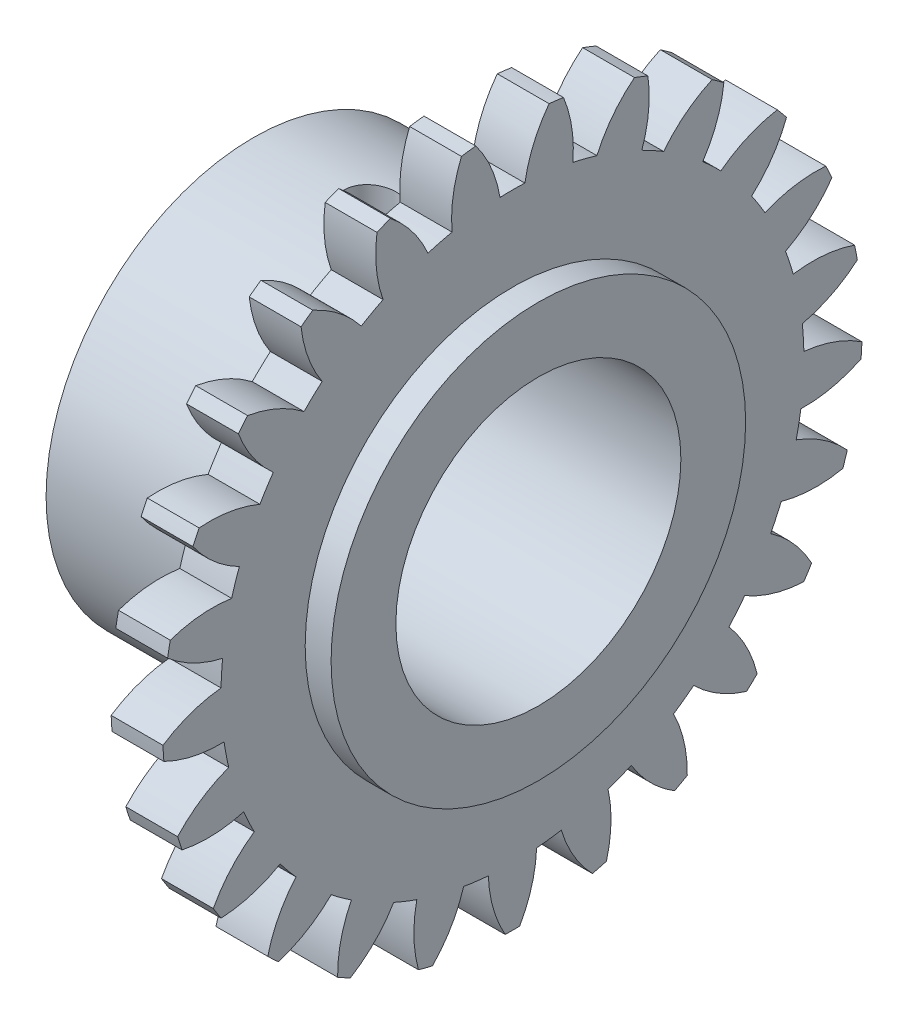
SolidWorks part; units mm, degrees
material "Alliage de zinc AC41A, brut"
ref_plane "Plane1" through (0, 0, 0) normal (0, 0, 1) x (1, 0, 0)
ref_plane "Plane2" through (0, 0, 0) normal (0, 1, 0) x (1, 0, 0)
ref_plane "Plane3" through (0, 0, 0) normal (1, 0, 0) x (0, 0, -1)
sketch "HoldingSke" plane through (0, 0, 0) normal (0, 1, 0) x (1, 0, 0)
  line L0 (0, 0) -> (0.9063, -0.4226)
  line L1 (-15, 0) -> (100, 0) construction
  line L2 (0, 0) -> (-2.1039, 2.3779)
  line L3 (0, 0) -> (-11.863, 4.5341)
  line L4 (0, 0) -> (7.8269, 3.6497)
  line L5 (0, 0) -> (-46.8476, -17.4728)
  line L6 (0, 0) -> (-1.6579, -1.1186)
  line L7 (-2.1039, 2.3779) -> (8.6586, 51.2059)
  line L8 (-76.2, 54.61) -> (-75.9, 54.61)
  line L9 (-71.009, 38.7566) -> (-53.1078, 45.2721)
  line L10 (-76.2, 71.12) -> (104.1128, 71.12)
  line L11 (0, 0) -> (-2, 0)
  line L12 (-76.2, 101.6) -> (-76.162, 101.6)
  line L13 (24.9733, 27.94) -> (52.9518, 28.4284)
  line L14 (24.9733, 27.94) -> (24.9743, 27.94)
  line L15 (24.9733, 27.94) -> (100.4006, 29.5858)
  line L16 (-63.627, -1) -> (-12.827, -1)
  circle A0 centre (0, 0) radius 1
  circle A1 centre (0, 0) radius 11.249
  circle A2 centre (0, 0) radius 37.5
  circle A3 centre (0, 0) radius 5.5
  dimension "Num_teeth" = 25
  dimension "Pitch_radius" = 180.3128
  dimension "Width" = 2
  dimension "Thickness" = 2
sketch "BasProSke" plane through (0, 0, 0) normal (0, 1, 0) x (1, 0, 0)
  line L0 (-10, 0) -> (60, 0) construction
  line L1 (0, 0) -> (0, 13.5)
  line L2 (0, 0) -> (2, 0)
  line L3 (2, 0) -> (2, 13.5)
  line L4 (2, 13.5) -> (0, 13.5)
  dimension "Thickness" = 2
  dimension "Diameter" = 27
revolve "Base-Revolve" add sketch "BasProSke" angle 360 about L0
sketch "TooCutSke" plane through (0, 0, 0) normal (1, 0, 0) x (0, 0, -1)
  line L1 (0, 0) -> (0, 107) construction
  line L2 (0, 0) -> (-0.8514, 12.471) construction
  line L3 (0, 0) -> (-3.1282, 24.7619) construction
  line L4 (-0.8514, 12.471) -> (-1.5641, 12.3809) construction
  arc A0 (0.4801, 11.2388) -> (-0.4801, 11.2388) centre (0, 0) ccw
  arc A1 (1.4322, 13.4494) -> (-1.4322, 13.4494) centre (0, 0) ccw
  circle A2 centre (0, 0) radius 12.5 construction
  circle A3 centre (0, 0) radius 11.7462 construction
  arc A4 (-0.4801, 11.2388) -> (-1.4322, 13.4494) centre (-5.4133, 10.4244) ccw
  arc A5 (1.4322, 13.4494) -> (0.4801, 11.2388) centre (5.4133, 10.4244) ccw
extrude "ToothCut" cut sketch "TooCutSke" along normal through all
fillet "Breaks" [suppressed] radius 0.02 tangent propagation no
fillet "RootFillets" [suppressed] radius 0.251
pattern_circular "TeethCuts" count 25 every 14.4 about axis through (-10, 0, 0) along (1, 0, 0) of "ToothCut", "RootFillets", "Breaks"
sketch "HubNeaOneSke" plane through (0, 0, 0) normal (-1, 0, 0) x (0, 0, 1)
  circle A0 centre (0, 0) radius 11.249
  dimension "Diameter" = 22.498
extrude "HubNearOne" [suppressed] add sketch "HubNeaOneSke" along normal blind 48.0001
sketch "HubNeaBotSke" plane through (0, 0, 0) normal (-1, 0, 0) x (0, 0, 1)
  circle A0 centre (0, 0) radius 11.249
  dimension "Diameter" = 22.498
extrude "HubNearBoth" [suppressed] add sketch "HubNeaBotSke" along normal blind 24
ref_plane "FarPln" through (2, 0, 0) normal (1, 0, 0) x (0, 0, -1)
sketch "HubFarSke" plane through (2, 0, 0) normal (1, 0, 0) x (0, 0, -1)
  circle A0 centre (0, 0) radius 11.249
  dimension "Diameter" = 22.498
extrude "HubFar" [suppressed] add sketch "HubFarSke" along normal blind 24
sketch "BorSke" plane through (0, 0, 0) normal (1, 0, 0) x (0, 0, -1)
  circle A0 centre (0, 0) radius 5.5
  dimension "Diameter" = 11
extrude "Bore" cut sketch "BorSke" along normal mid plane 100.0001
sketch "KeySke" plane through (0, 0, 0) normal (1, 0, 0) x (0, 0, -1)
  line L0 (-0.4, 0) -> (-0.4, 5.8)
  line L1 (-0.4, 5.8) -> (0.4, 5.8)
  line L2 (0.4, 5.8) -> (0.4, 0)
  line L3 (0, 0) -> (0, 34) construction
  line L4 (-0.4, 0) -> (0.4, 0)
  dimension "Width" = 0.8
extrude "Keyway" [suppressed] cut sketch "KeySke" along normal mid plane 100.0001
pattern_circular "Keyway2" [suppressed] count 2 every 90 about axis through (-10, 0, 0) along (1, 0, 0)
sketch "Esquisse1" plane through (2, 0, 0) normal (1, 0, 0) x (0, 0, -1)
  circle A0 centre (0, 0) radius 5.5
  circle A1 centre (0, 0) radius 8
  dimension "D1" = 11
  dimension "D2" = 16
extrude "Boss.-Extru.1" add sketch "Esquisse1" along normal blind 1
sketch "Esquisse2" plane through (0, 0, 0) normal (-1, 0, 0) x (0, 0, 1)
  circle A0 centre (0, 0) radius 8
  circle A1 centre (0, 0) radius 5.5
  dimension "D1" = 16
  dimension "D2" = 11
extrude "Boss.-Extru.2" add sketch "Esquisse2" along normal blind 8
sketch "Esquisse7" plane through (0, 0, 0) normal (0, 1, 0) x (1, 0, 0)
  line L0 (0, 8) -> (0, -8) construction
  point P0 (-3.5, 0)
  dimension "D1" = 3.5
hole_wizard "Diamètre du perçage Ø2.0 (2)1" positions "Esquisse7" profile "Esquisse4" hole size "Ø2.0" standard "ISO" end condition through all
sketch "Esquisse4" plane through (-3.5, 0, 0) normal (1, 0, 0) x (0, 0, -1)
  line L0 (0, 0) -> (0, 13.4257)
  line L1 (0, 13.4257) -> (1, 13.4257)
  line L2 (1, 13.4257) -> (1, 0)
  line L5 (1, 0) -> (0, 0)
  line L11 (0, -6.35) -> (0, 107.95) construction
  dimension "Diamètre du perçage jusqu'au prochain" = 2
  dimension "Profondeur du perçage jusqu'au prochain" = 13.4257
cosmetic thread "Représentation de filetage1" parameters "D2"=3
equation "' \"Module@HoldingSke\" = 6.35"
equation "' \"Num_teeth@HoldingSke\" = 12"
equation "' \"Ap@HoldingSke\" =  20"
equation "' \"Ap@HoldingSke\" = 20"
equation "' \"Width@HoldingSke\" = 0.5 * 25.4"
equation "' \"Hub_dia@HoldingSke\"= 1 * 25.4"
equation "' \"Hub_dia@HoldingSke\" = 1 * 25.4"
equation "' \"Overall_len@HoldingSke\" = 1.0 * 25.4"
equation "' \"Bore@HoldingSke\" = 0.75 * 25.4"
equation "' \"T_dim@HoldingSke\" = 0.1 * 25.4"
equation "' \"Width@KeySke\" = 0.25 * 25.4"
equation "' \"Show_teeth@HoldingSke\" = 13"
equation "' \"Backlash@HoldingSke\" = 0.009 * 25.4"
equation "' \"Addendum_fac@HoldingSke\" = 1.0"
equation "' \"Dedendum_fac@HoldingSke\" = 1.25"
equation "' \"Dedendum_add@HoldingSke\" = 0.00005 * 25.4"
equation "' \"Clearance_fac@HoldingSke\" = 0.25"
equation "\"Pitch@HoldingSke\" = 1 / \"Module@HoldingSke\""
equation "\"Overcut_dia@TooCutSke\" = (\"Num_teeth@HoldingSke\" + 2 * \"Addendum_fac@HoldingSke\") / \"Pitch@HoldingSke\" + 0.002 * 25.4"
equation "\"Pitch_dia@TooCutSke\" = \"Num_teeth@HoldingSke\" / \"Pitch@HoldingSke\""
equation "\"Base_dia@TooCutSke\" = \"Num_teeth@HoldingSke\" / \"Pitch@HoldingSke\" * cos((\"Ap@HoldingSke\"  * 3.14159265 / 180))"
equation "\"Root_dia@TooCutSke\" = (\"Num_teeth@HoldingSke\" + 2) / \"Pitch@HoldingSke\" - 2 * (\"Addendum_fac@HoldingSke\" + \"Dedendum_fac@HoldingSke\") / \"Pitch@HoldingSke\" - \"Dedendum_add@HoldingSke\" * 2"
equation "\"Half_ang@TooCutSke\" = 180 / \"Num_teeth@HoldingSke\""
equation "\"Half_CT@TooCutSke\" = \"Num_teeth@HoldingSke\" / \"Pitch@HoldingSke\" * sin((3.14159265 / 2 / \"Num_teeth@HoldingSke\")) / 2 - 7 * \"Backlash@HoldingSke\" / 4"
equation "\"Flank_rad@TooCutSke\" = \"Num_teeth@HoldingSke\" / \"Pitch@HoldingSke\" / 5"
equation "\"Radius@RootFillets\" = \"Clearance_fac@HoldingSke\" / \"Pitch@HoldingSke\" + \"Dedendum_add@HoldingSke\""
equation "\"Break_rad@Breaks\" = 0.02 / \"Pitch@HoldingSke\""
equation "\"Thickness@HoldingSke\" = \"Width@HoldingSke\""
equation "\"OAL@HoldingSke\" = \"Thickness@HoldingSke\""
equation "\"MHD@HoldingSke\" = (\"Num_teeth@HoldingSke\" + 2) / \"Pitch@HoldingSke\" - 2 * (\"Addendum_fac@HoldingSke\" + \"Dedendum_fac@HoldingSke\")  / \"Pitch@HoldingSke\" - \"Dedendum_add@HoldingSke\" * 2"
equation "\"MHD@HoldingSke\" = ((sgn( \"MHD@HoldingSke\" - \"Hub_dia@HoldingSke\" )-1)*( \"MHD@HoldingSke\" - \"Hub_dia@HoldingSke\" ))/-2+ \"Hub_dia@HoldingSke\""
equation "\"OAL@HoldingSke\" = ((sgn( \"OAL@HoldingSke\" - \"Overall_len@HoldingSke\" )+1)*( \"OAL@HoldingSke\" - \"Overall_len@HoldingSke\" ))/2 + \"Overall_len@HoldingSke\" + 0.000002 * 25.4"
equation "\"Num_teeth@TeethCuts\" = int( \"Show_teeth@HoldingSke\" ) + 1"
equation "\"Num_teeth@TeethCuts\" = ((sgn( \"Num_teeth@TeethCuts\" - \"Num_teeth@HoldingSke\" )-1)*( \"Num_teeth@TeethCuts\" - \"Num_teeth@HoldingSke\" ))/-2+ \"Num_teeth@HoldingSke\""
equation "\"Num_teeth@TeethCuts\" = ((sgn( \"Num_teeth@TeethCuts\" - 2.0)+1)*( \"Num_teeth@TeethCuts\" - 2.0))/2 +2.0"
equation "\"Angle@TeethCuts\" = 360.0 / \"Num_teeth@HoldingSke\""
equation "\"Diameter@BasProSke\" = (\"Num_teeth@HoldingSke\" + 2 * \"Addendum_fac@HoldingSke\") / \"Pitch@HoldingSke\""
equation "\"Thickness@BasProSke\"  = \"Thickness@HoldingSke\""
equation "' \"Fillet_rad@BasProSke\" =  \"Thickness@HoldingSke\" * 0.05"
equation "' \"Fillet_rad@BasProSke\" = \"Thickness@HoldingSke\" * 0.05"
equation "\"MHD@HoldingSke\" = ((sgn( \"MHD@HoldingSke\" - \"Root_dia@TooCutSke\" )-1)*( \"MHD@HoldingSke\" - \"Root_dia@TooCutSke\" ))/-2+ \"Root_dia@TooCutSke\""
equation "\"Diameter@HubNeaOneSke\" = \"MHD@HoldingSke\""
equation "\"Length@HubNearOne\" = \"OAL@HoldingSke\" - \"Thickness@BasProSke\""
equation "\"Diameter@HubNeaBotSke\" = \"MHD@HoldingSke\""
equation "\"Length@HubNearBoth\" = ( \"OAL@HoldingSke\" - \"Thickness@BasProSke\" ) / 2.0"
equation "\"Thickness@FarPln\" = \"Thickness@BasProSke\""
equation "\"Diameter@HubFarSke\" = \"MHD@HoldingSke\""
equation "\"Length@HubFar\" = ( \"OAL@HoldingSke\" - \"Thickness@BasProSke\" ) / 2.0"
equation "\"Diameter@BorSke\" = \"MBD@HoldingSke\""
equation "\"D1@Bore\" = \"OAL@HoldingSke\" * 2.0"
equation "\"D1@Keyway\" = \"OAL@HoldingSke\" * 2.0"
equation "\"Offset@KeySke\" = \"T_dim@HoldingSke\" + \"MBD@HoldingSke\" / 2.0"
